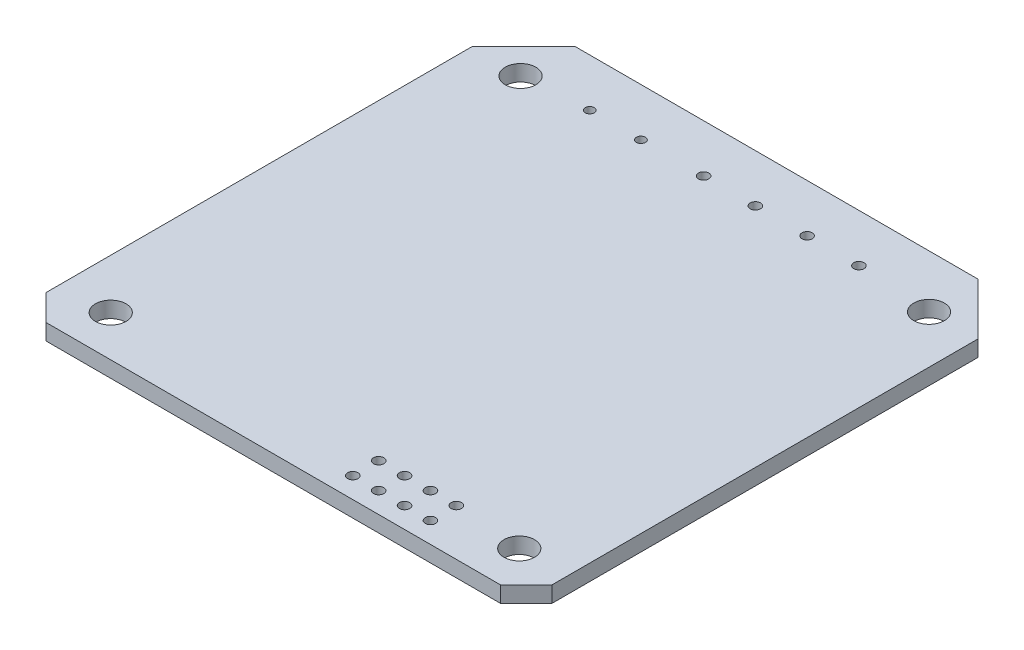
SolidWorks part; units mm, degrees
ref_plane "Front Plane" through (0, 0, 0) normal (0, 0, 1) x (1, 0, 0)
ref_plane "Top Plane" through (0, 0, 0) normal (0, 1, 0) x (1, 0, 0)
ref_plane "Right Plane" through (0, 0, 0) normal (1, 0, 0) x (0, 0, -1)
sketch "Sketch1" plane through (0, 0, 0) normal (0, 1, 0) x (1, 0, 0)
  line L1 (-24.8285, -24.7015) -> (24.8285, -24.7015)
  line L2 (-24.8285, -24.7015) -> (-24.8285, 24.7015)
  line L3 (-24.8285, 24.7015) -> (24.8285, 24.7015)
  line L4 (24.8285, -24.7015) -> (24.8285, 24.7015)
  line L5 (-24.8285, -24.7015) -> (24.8285, 24.7015) construction
  line L6 (-24.8285, 24.7015) -> (24.8285, -24.7015) construction
  point P0 (0, 0)
  dimension "D1" = 49.403
  dimension "D2" = 49.657
extrude "Boss-Extrude1" add sketch "Sketch1" along normal blind 1.5748
chamfer "Chamfer1" distance 5.08 angle 45 2 edges at (-24.8285, 0.7874, -24.7015) (24.8285, 0.7874, -24.7015)
chamfer "Chamfer2" distance 2.54 angle 45 2 edges at (24.8285, 0.7874, 24.7015) (-24.8285, 0.7874, 24.7015)
sketch "Sketch2" plane through (0, 1.5748, 0) normal (0, 1, 0) x (1, 0, 0)
  line L0 (-24.8285, 19.6215) -> (-24.8285, -22.1615) construction
  line L1 (-19.9517, -20.6883) -> (20.1295, -20.6883)
  line L2 (-19.9517, -20.6883) -> (-19.9517, 19.5199)
  line L3 (-19.9517, 19.5199) -> (20.1295, 19.5199)
  line L4 (20.1295, -20.6883) -> (20.1295, 19.5199)
  line L7 (-22.2885, -24.7015) -> (22.2885, -24.7015) construction
  circle A0 centre (-19.9517, 19.5199) radius 1.5
  circle A1 centre (20.1295, 19.5199) radius 1.5
  circle A2 centre (-19.9517, -20.6883) radius 1.5
  circle A3 centre (20.1295, -20.6883) radius 1.5
  circle A4 centre (5.7785, -22.6695) radius 0.508
  circle A5 centre (8.3185, -22.6695) radius 0.508
  circle A6 centre (10.8585, -22.6695) radius 0.508
  circle A7 centre (13.3985, -22.6695) radius 0.508
  circle A8 centre (8.3185, -20.1295) radius 0.508
  circle A9 centre (10.8585, -20.1295) radius 0.508
  circle A10 centre (13.3985, -20.1295) radius 0.508
  circle A11 centre (5.7785, -20.1295) radius 0.508
  dimension "D1" = 3
  dimension "D6" = 1.016
  dimension "D2" = 4.8768
  dimension "D3" = 40.0812
  dimension "D4" = 40.2082
  dimension "D5" = 4.0132
  dimension "D9" = 30.607
  dimension "D10" = 2.032
  dimension "D11" = 2.54
  dimension "D12" = 2.54
  dimension "D7" = 4
  dimension "D8" = 2
extrude "Cut-Extrude1" cut sketch "Sketch2" against normal through all contours L3 A0 L2 | L2 A0 L3 | L4 A1 L3 | L3 A1 L4 | L1 A3 L4 | L4 A3 L1 | L2 A2 L1 | L1 A2 L2 | A11 | A8 | A9 | A10 | A7 | A6 | A5 | A4 region at (-19.3151, 1.5748, 20.0517) region at (-20.1639, 1.5748, 20.9005) region at (19.4929, 1.5748, 20.0517) region at (20.3417, 1.5748, 20.9005) region at (-20.1639, 1.5748, -19.7321) region at (-19.3151, 1.5748, -18.8833) region at (19.4929, 1.5748, -18.8833) region at (20.3417, 1.5748, -19.7321) region at (5.7785, 1.5748, 22.6695) region at (8.3185, 1.5748, 22.6695) region at (10.8585, 1.5748, 22.6695) region at (13.3985, 1.5748, 22.6695) region at (8.3185, 1.5748, 20.1295) region at (10.8585, 1.5748, 20.1295) region at (13.3985, 1.5748, 20.1295) region at (5.7785, 1.5748, 20.1295)
ref_axis "Axis1" through (5.7785, 0, 22.6695) along (0, 1, 0)
sketch "Sketch3" plane through (0, 1.5748, 0) normal (0, 1, 0) x (1, 0, 0)
  line L0 (-13.6514, 20.0025) -> (12.7635, 20.0025) construction
  line L1 (19.7485, 24.7015) -> (-19.7485, 24.7015) construction
  line L2 (24.8285, -22.1615) -> (24.8285, 19.6215) construction
  circle A0 centre (12.7635, 20.0025) radius 0.508
  circle A1 centre (7.6835, 20.0025) radius 0.508
  circle A2 centre (2.6035, 20.0025) radius 0.508
  circle A3 centre (-2.4765, 20.0025) radius 0.508
  circle A4 centre (-8.6233, 20.0025) radius 0.4445
  circle A5 centre (-13.6514, 20.0025) radius 0.4445
  dimension "D3" = 1.016
  dimension "D6" = 0.889
  dimension "D1" = 4.699
  dimension "D2" = 12.065
  dimension "D5" = 5.08
  dimension "D8" = 6.1468
  dimension "D9" = 5.0281
  dimension "D4" = 4
  dimension "D7" = 2
extrude "Cut-Extrude2" cut sketch "Sketch3" against normal blind 2.54 contours A5 | A4 L0 | L0 A4 | A3 L0 | L0 A3 | A2 L0 | L0 A2 | A1 L0 | L0 A1 | A0 region at (12.7635, 1.5748, -20.4961) region at (7.6835, 1.5748, -20.2181) region at (7.6835, 1.5748, -19.7869) region at (2.6035, 1.5748, -20.2181) region at (2.6035, 1.5748, -19.7869) region at (-2.4765, 1.5748, -20.2181) region at (-2.4765, 1.5748, -19.7869) region at (-8.6233, 1.5748, -20.1912) region at (-8.6233, 1.5748, -19.8138) region at (-14.0833, 1.5748, -20.0025)
